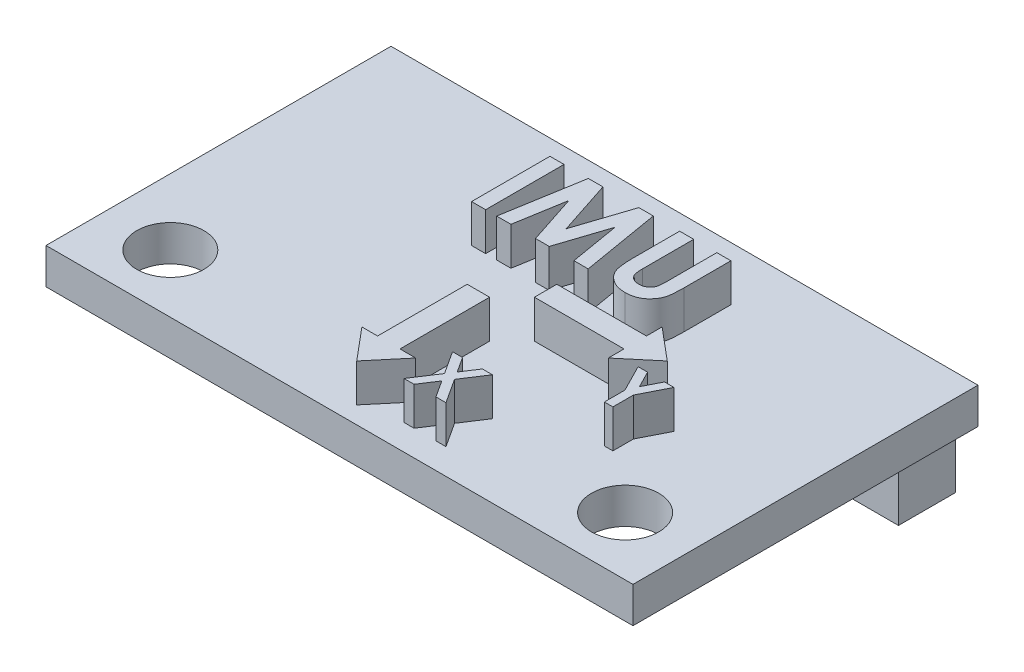
SolidWorks part; units mm, degrees
ref_plane "정면" through (0, 0, 0) normal (0, 0, 1) x (1, 0, 0)
ref_plane "윗면" through (0, 0, 0) normal (0, 1, 0) x (1, 0, 0)
ref_plane "우측면" through (0, 0, 0) normal (1, 0, 0) x (0, 0, -1)
sketch "스케치1" plane through (0, 0, 0) normal (0, 1, 0) x (1, 0, 0)
  line L0 (0, 0) -> (0, 14.3289) construction
  line L1 (-13.1, -7.7) -> (13.1, -7.7)
  line L2 (-13.1, -7.7) -> (-13.1, 7.7)
  line L3 (-13.1, 7.7) -> (13.1, 7.7)
  line L4 (13.1, -7.7) -> (13.1, 7.7)
  line L5 (-13.1, -7.7) -> (13.1, 7.7) construction
  line L6 (-13.1, 7.7) -> (13.1, -7.7) construction
  line L8 (-12.5, 4.75) -> (12.5, 4.75)
  line L9 (-12.5, 4.75) -> (-12.5, 7.3)
  line L10 (-12.5, 7.3) -> (12.5, 7.3)
  line L11 (12.5, 4.75) -> (12.5, 7.3)
  line L12 (-12.5, 4.75) -> (12.5, 7.3) construction
  line L13 (-12.5, 7.3) -> (12.5, 4.75) construction
  circle A0 centre (-10.15, -5.1) radius 1.5
  circle A1 centre (10.15, -5.1) radius 1.5
  point P0 (0, 0)
  point P10 (0, 6.025)
  dimension "D3" = 3
  dimension "D1" = 26.2
  dimension "D2" = 15.4
  dimension "D4" = 20.3
  dimension "D5" = 2.6
  dimension "D6" = 2.55
  dimension "D7" = 25
  dimension "D8" = 0.4
extrude "보스-돌출1" add sketch "스케치1" along normal blind 1.6 contours L1 L4 L3 L2 L11 L8 L9 L10 A0 A1 | L8 L11 L10 L9 region at (0, 0, 0.9582) region at (0, 0, -6.025)
extrude "보스-돌출2" add sketch "스케치1<3>" against normal blind 2.65 contours L8 L11 L10 L9
sketch "스케치1<3>" plane through (0, 0, 0) normal (0, 1, 0) x (1, 0, 0) same geometry as "스케치1"
sketch "스케치2" plane through (0, 1.6, 0) normal (0, 1, 0) x (1, 0, 0)
  line L0 (0, 0) -> (0, -10.3988) construction
  line L1 (0.5, -1.5) -> (-0.5, -1.5)
  line L2 (-0.5, -1.5) -> (-0.5, -5.5)
  line L3 (0.5, -1.5) -> (0.5, -5.5)
  line L4 (-0.5, -5.5) -> (-1.2, -5.5)
  line L5 (0.5, -5.5) -> (1.2, -5.5)
  line L6 (-1.2, -5.5) -> (0, -6.9301)
  line L7 (1.2, -5.5) -> (0, -6.9301)
  line L8 (-5.5, 1.2) -> (-6.9301, 0) [skipped]
  line L9 (-5.5, -1.2) -> (-6.9301, 0) [skipped]
  line L10 (-5.5, -0.5) -> (-5.5, -1.2) [skipped]
  line L11 (-1.5, -0.5) -> (-5.5, -0.5) [skipped]
  line L12 (-1.5, -0.5) -> (-1.5, 0.5) [skipped]
  line L13 (-1.5, 0.5) -> (-5.5, 0.5) [skipped]
  line L14 (-5.5, 0.5) -> (-5.5, 1.2) [skipped]
  line L15 (1.2, 5.5) -> (0, 6.9301) [skipped]
  line L16 (-1.2, 5.5) -> (0, 6.9301) [skipped]
  line L17 (-0.5, 5.5) -> (-1.2, 5.5) [skipped]
  line L18 (-0.5, 1.5) -> (-0.5, 5.5) [skipped]
  line L19 (-0.5, 1.5) -> (0.5, 1.5) [skipped]
  line L20 (0.5, 1.5) -> (0.5, 5.5) [skipped]
  line L21 (0.5, 5.5) -> (1.2, 5.5) [skipped]
  line L22 (5.5, -1.2) -> (6.9301, 0)
  line L23 (5.5, 1.2) -> (6.9301, 0)
  line L24 (5.5, 0.5) -> (5.5, 1.2)
  line L25 (1.5, 0.5) -> (5.5, 0.5)
  line L26 (1.5, 0.5) -> (1.5, -0.5)
  line L27 (1.5, -0.5) -> (5.5, -0.5)
  line L28 (5.5, -0.5) -> (5.5, -1.2)
  text T0 "<b>IMU</b>" font "Century Gothic" height 3.5
  text T1 "<b>X</b>" font "Century Gothic" height in points 8
  text T2 "<b>Y</b>" font "Century Gothic" height in points 8
  point P4 (0, -1.5)
  point P5 (2.6145, 1.2159)
  point P12 (-3.9273, 1.2)
  point P13 (-3.9135, 1.7943)
  point P36 (0, 0)
  point P37 (0, 0)
  point P38 (3.0414, -6.1798)
  point P39 (2.9175, -5.7804)
  point P40 (2.0361, -6.6067)
  point P41 (1.6642, -6.5516)
  point P43 (0, 0)
  point P44 (0, 0)
  point P45 (0, 0)
  point P46 (0, 0)
  point P47 (0, 0)
  point P48 (0, 0)
  point P50 (0.589, 0.566)
  point P52 (6.6596, -3.1618)
  point P53 (6.4337, -2.9891)
  dimension "D1" = 1
  dimension "D2" = 0.7
  dimension "D3" = 130
  dimension "D4" = 4
  dimension "D5" = 1.5
  dimension "D6" = 4
extrude "보스-돌출3" add sketch "스케치2" along normal blind 1.7
